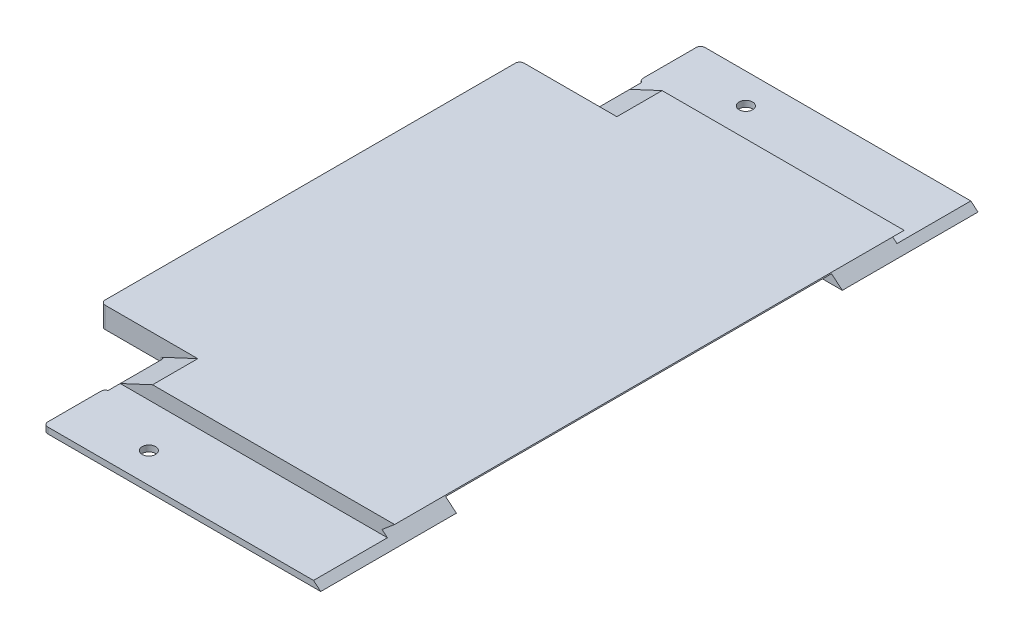
SolidWorks part; units mm, degrees
material "ABS"
ref_plane "Ebene vorne" through (0, 0, 0) normal (0, 0, 1) x (1, 0, 0)
ref_plane "Ebene oben" through (0, 0, 0) normal (0, 1, 0) x (1, 0, 0)
ref_plane "Ebene rechts" through (0, 0, 0) normal (1, 0, 0) x (0, 0, -1)
sketch "Skizze2" plane through (0, 0, 0) normal (0, 1, 0) x (1, 0, 0)
  line L5 (0, 0) -> (-112.5, 0)
  line L6 (0, 0) -> (0, 109)
  line L7 (0, 109) -> (-112.5, 109)
  line L8 (-112.5, 0) -> (-112.5, 109)
  dimension "D1" = 112.5
  dimension "D2" = 109
extrude "Aufsatz-Linear austragen1" add sketch "Skizze2" along normal blind 2
sketch "Skizze3" plane through (0, 2, 0) normal (0, 1, 0) x (1, 0, 0)
  line L5 (-112.5, 109) -> (-92, 109)
  line L6 (-112.5, 109) -> (-112.5, 88.5)
  line L7 (-112.5, 88.5) -> (-92, 88.5)
  line L8 (-92, 109) -> (-92, 88.5)
  dimension "D1" = 20.5
  dimension "D2" = 20.5
extrude "Schnitt-Linear austragen1" cut sketch "Skizze3" against normal through all
sketch "Skizze5" plane through (0, 2, 0) normal (0, 1, 0) x (1, 0, 0)
  line L9 (-92, 88.5) -> (0, 88.5) construction
  line L10 (-92, 88.5) -> (-92, 0) construction
  line L11 (-92, 0) -> (0, 0) construction
  line L12 (0, 88.5) -> (0, 0) construction
  line L13 (0, 0) -> (-91, 0)
  line L14 (0, 0) -> (0, 84.5)
  line L15 (0, 84.5) -> (-91, 84.5)
  line L16 (-91, 0) -> (-91, 84.5)
  dimension "D1" = 1
  dimension "D2" = 4
extrude "Aufsatz-Linear austragen2" add sketch "Skizze5" along normal blind 5
sketch "Skizze6" plane through (0, 2, 0) normal (0, 1, 0) x (1, 0, 0)
  line L1 (-92, 94) -> (-83.4, 94)
  line L2 (-92, 94) -> (-92, 104)
  line L3 (-92, 104) -> (-83.4, 104)
  line L4 (-83.4, 94) -> (-83.4, 104)
  line L6 (-92, 88.5) -> (-92, 109) construction
  point P4 (-92, 99)
  dimension "D1" = 10
  dimension "D2" = 8.6
  dimension "D3" = 10
extrude "Schnitt-Linear austragen2" [suppressed] cut sketch "Skizze6" against normal through all
sketch "Skizze8" plane through (0, 2, 0) normal (0, 1, 0) x (1, 0, 0)
  line L0 (-91, 84.5) -> (-91, 0) construction
  line L1 (-112.5, 88.5) -> (-91, 88.5)
  line L2 (-112.5, 88.5) -> (-112.5, 69.5)
  line L3 (-112.5, 69.5) -> (-91, 69.5)
  line L4 (-91, 88.5) -> (-91, 69.5)
  line L5 (-112.5, 88.5) -> (-112.5, 0) construction
  dimension "D1" = 19
extrude "Schnitt-Linear austragen3" cut sketch "Skizze8" against normal through all
sketch "Skizze9" plane through (0, 2, 0) normal (0, 1, 0) x (1, 0, 0)
  line L4 (-91, 69.5) -> (-112.5, 69.5)
  line L5 (-112.5, 69.5) -> (-112.5, 0)
  line L6 (-112.5, 0) -> (-91, 0)
  line L7 (-91, 0) -> (-91, 69.5)
  line L8 (-91, 69.5) -> (-112.5, 69.5)
  line L9 (-112.5, 69.5) -> (-112.5, 0)
  line L10 (-112.5, 0) -> (-91, 0)
  line L11 (-91, 0) -> (-91, 69.5)
  dimension "D1" = 0
extrude "Aufsatz-Linear austragen3" add sketch "Skizze9" along normal up to surface (5 mm away) up to face at (-45.5, 7, -42.25)
chamfer "Fase1" distance 5 angle 65 1 edges at (-91, 7, -77) first distance on face at (-91, 3, -80.8333)
sketch "Skizze10" plane through (0, 0, 0) normal (0, 1, 0) x (1, 0, 0)
  line L1 (42.875, -64) -> (-42.875, -64)
  line L2 (42.875, -64) -> (42.875, 64)
  line L3 (42.875, 64) -> (-42.875, 64)
  line L4 (-42.875, -64) -> (-42.875, 64)
  line L5 (42.875, -64) -> (-42.875, 64) construction
  line L6 (42.875, 64) -> (-42.875, -64) construction
  point P0 (0, 0)
  dimension "D1" = 128
  dimension "D2" = 85.75
extrude "Schnitt-Linear austragen4" cut sketch "Skizze10" along normal blind 3
fillet "Verrundung1" radius 1 1 edges at (-42.875, 1.5, -64)
hole_wizard "Durchgangsloch für M41" positions "Skizze11" profile "Skizze12" hole size "M4" standard "ANSI Metrisch"
sketch "Skizze11" plane through (0, 0, 0) normal (0, -1, 0) x (-1, 0, 0)
  line L0 (0, 109) -> (92, 109) construction
  line L2 (92, 88.5) -> (92, 109) construction
  point P0 (67, 99)
  dimension "D1" = 10
  dimension "D2" = 25
sketch "Skizze12" plane through (-67, 0, -99) normal (1, 0, 0) x (0, 0, -1)
  line L0 (0, 0) -> (0, 6)
  line L1 (0, 6) -> (2.25, 6)
  line L2 (2.25, 6) -> (2.25, 0)
  line L5 (2.25, 0) -> (0, 0)
  line L10 (0, 6) -> (-2.25, 6) construction
  line L11 (0, -6.35) -> (0, 107.95) construction
  dimension "Bohrerdurchmesser" = 4.5
  dimension "Bohrungstiefe" = 6
  dimension "Spitzenwinkel" = 180
fillet "Verrundung2" radius 1.5 4 edges at (-92, 1, -88.5) (-112.5, 3.5, -69.5) (-92, 1, -109) (-91, 1, -69.5)
mirror "Spiegeln1" about plane through (0, 2, 0) normal (0, 0, -1) of bodies 111 103
mirror "Spiegeln2" about plane through (0, 2, 0) normal (-1, 0, 0) of bodies 104
sketch "Skizze15" plane through (0, 0, -109) normal (0, 0, -1) x (-1, 0, 0)
  line L0 (0, 0) -> (4.1711, 3.5)
  line L1 (4.1711, 3.5) -> (0, 7)
  line L2 (-80.2775, 7) -> (80.2775, 7) construction
  line L3 (0, 7) -> (-112.5, 7)
  line L4 (-112.5, 7) -> (-112.5, 0)
  line L5 (-112.5, 0) -> (0, 0)
  dimension "D1" = 40
extrude "Schnitt-Linear austragen7" cut sketch "Skizze15" against normal through all
sketch "Skizze16" [suppressed] plane through (0, 0, 0) normal (0, 0, 1) x (1, 0, 0)
  line L0 (0, 0) -> (4.1711, 3.5)
  line L1 (4.1711, 3.5) -> (0, 7)
  line L6 (0, 7) -> (112.5, 7)
  line L7 (112.5, 7) -> (112.5, 0)
  line L8 (112.5, 0) -> (0, 0)
  line L9 (80.2775, 7) -> (-80.2775, 7) construction
  dimension "D1" = 40
extrude "Schnitt-Linear austragen8" [suppressed] cut sketch "Skizze16" against normal through all both and the other way through all
